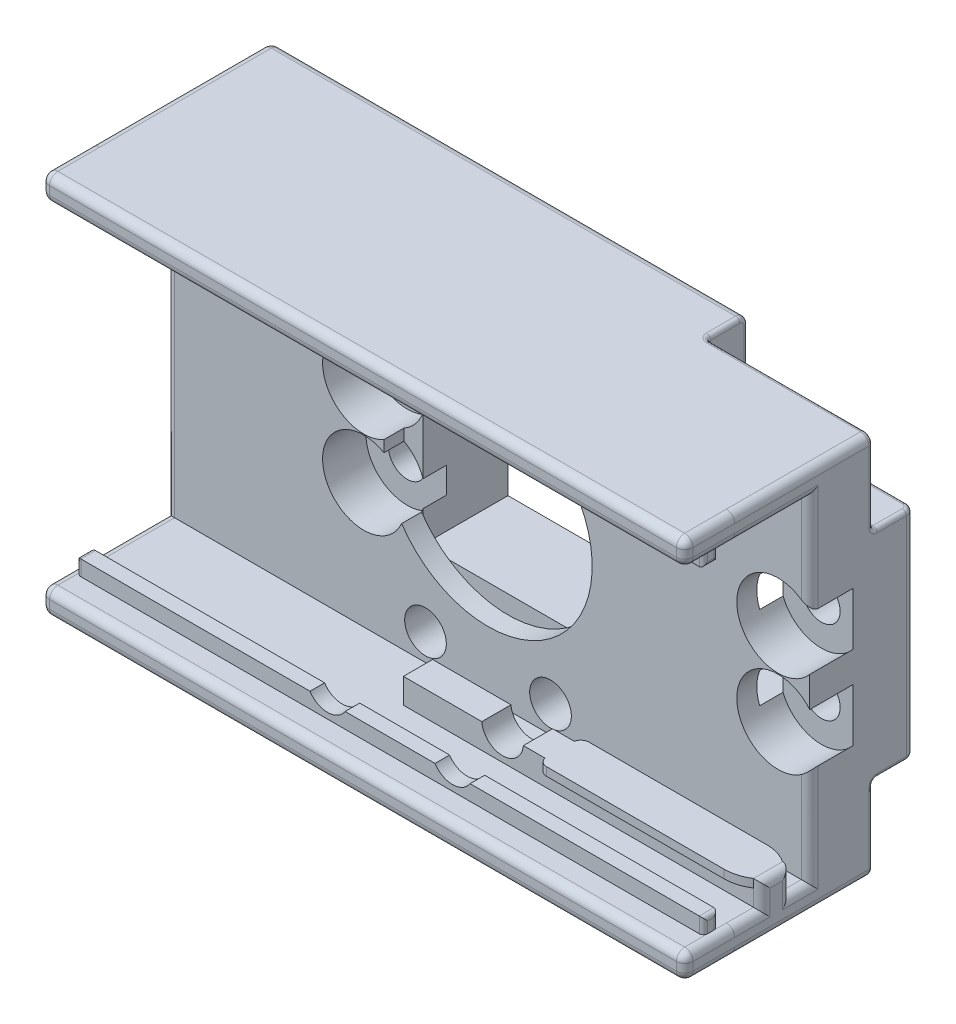
SolidWorks part; units mm, degrees
ref_plane "Front Plane" through (0, 0, 0) normal (0, 0, 1) x (1, 0, 0)
ref_plane "Top Plane" through (0, 0, 0) normal (0, 1, 0) x (1, 0, 0)
ref_plane "Right Plane" through (0, 0, 0) normal (1, 0, 0) x (0, 0, -1)
sketch "Sketch2" plane through (0, 0, 0) normal (0, 0, 1) x (1, 0, 0)
  line L0 (-38.6, 0) -> (38.6, 0) construction
  line L1 (-38.6, 20) -> (38.6, 20)
  line L2 (-38.6, 20) -> (-38.6, -20)
  line L3 (-38.6, -20) -> (38.6, -20)
  line L4 (38.6, 20) -> (38.6, -20)
  line L5 (0, 20) -> (0, -20) construction
  circle A0 centre (0, 0) radius 12.5
  point P13 (0, 0)
  dimension "D1" = 25
  dimension "D2" = 40
  dimension "D3" = 77.2
extrude "Boss-Extrude1" add sketch "Sketch2" along normal blind 2.4
sketch "Sketch5" plane through (0, 0, 0) normal (0, 0, -1) x (-1, 0, 0)
  line L0 (38.6, -20) -> (-38.6, -20) construction
  line L1 (-30.2, 10.3) -> (10.2, 10.3)
  line L2 (-30.2, 10.3) -> (-30.2, -10.3)
  line L3 (-30.2, -10.3) -> (10.2, -10.3)
  line L4 (10.2, 10.3) -> (10.2, -10.3)
  line L5 (-38.6, 20) -> (21.7, 20)
  line L6 (-38.6, 20) -> (-38.6, -20)
  line L7 (-38.6, -20) -> (21.7, -20)
  line L8 (21.7, 20) -> (21.7, -20)
  point P4 (10.2, 0)
  point P13 (-30.2, 0)
  dimension "D1" = 10.2
  dimension "D2" = 30.2
  dimension "D3" = 11.5
  dimension "D4" = 20.6
extrude "Boss-Extrude4" add sketch "Sketch5" along normal blind 10.2
sketch "Sketch6" plane through (0, 0, -10.2) normal (0, 0, -1) x (-1, 0, 0)
  line L1 (-36.1, -0.85) -> (-30.2, -0.85)
  line L2 (-36.1, -0.85) -> (-36.1, 0.85)
  line L3 (-36.1, 0.85) -> (-30.2, 0.85)
  line L4 (-30.2, -0.85) -> (-30.2, 0.85)
  line L5 (-30.2, 10.3) -> (-30.2, -10.3) construction
  dimension "D1" = 1.7
  dimension "D2" = 5.9
extrude "Cut-Extrude1" cut sketch "Sketch6" against normal blind 2
sketch "Sketch9" plane through (0, 20, 0) normal (0, 1, 0) x (1, 0, 0)
  line L0 (-21.7, 10.2) -> (38.6, 10.2) construction
  line L1 (-38.6, 10.2) -> (4.4, 10.2)
  line L2 (-38.6, 10.2) -> (-38.6, -12.4)
  line L3 (-38.6, -12.4) -> (4.4, -12.4)
  line L4 (4.4, 10.2) -> (4.4, -12.4)
  line L5 (38.6, -2.4) -> (-38.6, -2.4) construction
  line L9 (-38.6, -2.4) -> (-38.6, 0) construction
  dimension "D1" = 10
  dimension "D2" = 43
extrude "Boss-Extrude7" add sketch "Sketch9" along normal blind 3
sketch "Sketch10" plane through (0, 20, 0) normal (0, -1, 0) x (1, 0, 0)
  line L0 (4.4, 12.4) -> (4.4, 2.4) construction
  line L1 (-38.6, 8.15) -> (4.4, 8.15)
  line L2 (-38.6, 8.15) -> (-38.6, 4.65)
  line L3 (-38.6, 4.65) -> (4.4, 4.65)
  line L4 (4.4, 8.15) -> (4.4, 4.65)
  line L5 (-38.6, 12.4) -> (4.4, 12.4) construction
  dimension "D1" = 3.5
  dimension "D2" = 4.25
extrude "Boss-Extrude8" add sketch "Sketch10" along normal blind 3
sketch "Sketch20" plane through (4.4, 0, 0) normal (1, 0, 0) x (0, 0, -1)
  line L1 (-12.4, 23) -> (10.2, 23)
  line L2 (-12.4, 23) -> (-12.4, 20)
  line L3 (-12.4, 20) -> (10.2, 20)
  line L4 (10.2, 23) -> (10.2, 20)
extrude "Boss-Extrude9" add sketch "Sketch20" along normal up to surface (34.2 mm away) up to face at (38.6, 0, -3.9)
hole_wizard "Ø4.0mm Dowel Hole1" positions "Sketch12" profile "Sketch13" hole size "Ø4.0" standard "ANSI Metric" end condition through all
sketch "Sketch12" plane through (0, 0, -10.2) normal (0, 0, -1) x (-1, 0, 0)
  line L5 (-38.6, 23) -> (-38.6, -20) construction
  line L7 (10.2, -10.3) -> (10.2, 10.3) construction
  point P0 (-34.8, 5)
  point P10 (-34.8, -5)
  point P12 (14.9, -5)
  point P14 (14.9, 5)
  dimension "D1" = 3.8
  dimension "D2" = 4.7
sketch "Sketch13" plane through (34.8, 5, -10.2) normal (1, 0, 0) x (0, 1, 0)
  line L0 (0, 0) -> (0, 22.6)
  line L1 (0, 22.6) -> (2.25, 22.6)
  line L2 (2.25, 22.6) -> (2.25, 0)
  line L5 (2.25, 0) -> (0, 0)
  line L11 (0, -6.35) -> (0, 107.95) construction
  dimension "Thru Hole Dia." = 4.5
  dimension "Thru Hole Depth" = 22.6
sketch "Sketch17" plane through (0, 0, -10.2) normal (0, 0, -1) x (-1, 0, 0)
  line L0 (-15, 20.3) -> (15, 20.3) construction
  line L1 (15, 20.3) -> (15, 10.3) construction
  line L2 (15, 10.3) -> (-15, 10.3) construction
  line L3 (-15, 10.3) -> (-15, 20.3) construction
  line L4 (10.2, 10.3) -> (-30.2, 10.3) construction
  point P2 (0, 10.3)
  dimension "D1" = 10
  dimension "D2" = 30
hole_wizard "Ø2.0mm Dowel Hole1" positions "Sketch18" profile "Sketch19" hole size "Ø2.0" standard "ANSI Metric" end condition through all
sketch "Sketch18" plane through (0, 0, -10.2) normal (0, 0, -1) x (-1, 0, 0)
  line L3 (-7.5, 16.8) -> (7.5, 16.8) construction
  line L6 (-38.6, 23) -> (38.6, 23) construction
  point P0 (-7.5, 16.8)
  point P2 (7.5, 16.8)
  point P16 (0, 16.8)
  dimension "D1" = 15
  dimension "D2" = 6.2
sketch "Sketch19" plane through (7.5, 16.8, -10.2) normal (1, 0, 0) x (0, 1, 0)
  line L0 (0, 0) -> (0, 22.6)
  line L1 (0, 22.6) -> (1, 22.6)
  line L2 (1, 22.6) -> (1, 0)
  line L5 (1, 0) -> (0, 0)
  line L11 (0, -6.35) -> (0, 107.95) construction
  dimension "Thru Hole Dia." = 2
  dimension "Thru Hole Depth" = 22.6
mirror "Mirror10" about plane through (0, 0, 0) normal (0, 1, 0) of "Ø2.0mm Dowel Hole1"
pattern_circular "CirPattern1" count 2 over 360 about axis through (0, 0, 0) along (0, 0, 1) of "Boss-Extrude7", "Boss-Extrude8"
sketch "Sketch14" plane through (0, 0, 2.4) normal (0, 0, 1) x (1, 0, 0)
  circle A0 centre (-14.9, 5) radius 4.95
  circle A1 centre (-14.9, -5) radius 4.95
  circle A2 centre (-7.5, 16.8) radius 2.5
  circle A3 centre (7.5, 16.8) radius 2.5
  circle A9 centre (34.8, 5) radius 4.95
  circle A11 centre (34.8, -5) radius 4.95
  circle A12 centre (-7.5, -16.8) radius 2.5
  circle A13 centre (7.5, -16.8) radius 2.5
  dimension "D1" = 9.9
  dimension "D2" = 5
extrude "Cut-Extrude2" cut sketch "Sketch14" against normal blind 5.2 and the other way through all
sketch "Sketch22" plane through (-4.4, 0, 0) normal (-1, 0, 0) x (0, 0, 1)
  line L0 (12.4, -23) -> (12.4, -20) construction
  line L1 (-10.2, -23) -> (12.4, -23)
  line L2 (-10.2, -23) -> (-10.2, -20)
  line L3 (-10.2, -20) -> (12.4, -20)
  line L4 (12.4, -23) -> (12.4, -20)
  line L5 (12.4, -20) -> (8.15, -20) construction
extrude "Boss-Extrude10" add sketch "Sketch22" along normal up to surface (34.2 mm away) up to face at (-38.6, 13.3333, 2.9)
fillet "Fillet1" radius 1 39 edges at (38.6, 23, 1.1) (38.6, 20, 7.4) (38.6, -14.0861, 2.4) (38.6, -20, 3.525) (0, -20, 12.4) (38.6, -23, 1.1) (0, -23, 12.4) (0, -23, -10.2) (38.6, -20, 10.275) (38.6, -18.5, 8.15) (38.6, -18.5, 4.65) (38.6, -17, 6.4) (-30.15, 20, 0) (38.6, 14.0861, 2.4) (38.6, 0, -10.2) (-21.7, 0, -10.2) (-21.7, 0, 0) (-21.7, -20, -5.1) (-38.6, -20, -5.1) (-38.6, -20, 7.4) (-38.6, -21.5, 12.4) (-38.6, -23, 1.1) (-30.15, -20, -10.2) (-21.7, 20, -5.1) (-38.6, 0, 2.4) (-30.15, -20, 0) (-38.6, 0, 0) (-38.6, 20, -5.1) (-38.6, 20, 3.525) (0, 20, 12.4) (-38.6, 21.5, 12.4) (-30.15, 20, -10.2) (-38.6, 23, 1.1) (0, 23, 12.4) (0, 23, -10.2) (-38.6, 20, 10.275) (-38.6, 18.5, 8.15) (-38.6, 18.5, 4.65) (-38.6, 17, 6.4)
sketch "Sketch23" plane through (0, 0, -10.2) normal (0, 0, -1) x (-1, 0, 0)
  line L0 (-37.6, 23) -> (37.6, 23) construction
  line L1 (-18.6, 13) -> (-38.6, 13)
  line L2 (-18.6, 13) -> (-18.6, 23)
  line L3 (-18.6, 23) -> (-38.6, 23)
  line L4 (-38.6, 13) -> (-38.6, 23)
  line L5 (-18.6, -13) -> (-38.6, -13)
  line L6 (-18.6, -13) -> (-18.6, -23)
  line L7 (-18.6, -23) -> (-38.6, -23)
  line L8 (-38.6, -13) -> (-38.6, -23)
  line L9 (-38.6, -22) -> (-38.6, 22) construction
  line L10 (37.6, -23) -> (-37.6, -23) construction
  dimension "D1" = 20
  dimension "D2" = 10
  dimension "D3" = 20
  dimension "D4" = 10
extrude "Cut-Extrude3" cut sketch "Sketch23" against normal blind 5
fillet "Fillet2" radius 0.5 24 edges at (18.6, 22.7071, -9.9071) (38.3071, 22.7071, -5.2) (38.3071, -13, -9.9071) (38.3071, 13, -9.9071) (38.3071, -22.7071, -5.2) (18.6, -22.7071, -9.9071) (28.1, 23, -5.2) (28.1, 13, -10.2) (18.6, 17.5, -10.2) (18.6, 18, -5.2) (18.6, 23, -7.2) (28.6, 13, -5.2) (18.6, 13, -7.7) (38.6, 17.5, -5.2) (38.6, 13, -7.2) (18.6, -18, -5.2) (18.6, -13, -7.7) (28.1, -23, -5.2) (18.6, -23, -7.2) (38.6, -17.5, -5.2) (28.6, -13, -5.2) (38.6, -13, -7.2) (18.6, -17.5, -10.2) (28.1, -13, -10.2)
sketch "Sketch24" plane through (0, 0, 4.65) normal (0, 0, -1) x (-1, 0, 0)
  line L1 (37.6, 17) -> (12.6, 17)
  line L2 (37.6, 17) -> (37.6, 18)
  line L3 (37.6, 18) -> (12.6, 18)
  line L4 (12.6, 17) -> (12.6, 18)
  dimension "D1" = 1
  dimension "D2" = 25
extrude "Boss-Extrude11" add sketch "Sketch24" along normal blind 0.8
sketch "Sketch25" plane through (0, 0, 8.15) normal (0, 0, 1) x (1, 0, 0)
  line L1 (-37.6, 17) -> (-12.6, 17)
  line L2 (-37.6, 17) -> (-37.6, 18)
  line L3 (-37.6, 18) -> (-12.6, 18)
  line L4 (-12.6, 17) -> (-12.6, 18)
  dimension "D1" = 25
  dimension "D2" = 1
extrude "Boss-Extrude12" add sketch "Sketch25" along normal blind 0.8
fillet "Fillet3" radius 5 2 edges at (-37.6, 17.5, 3.85) (-37.6, 17.5, 8.95)
sketch "Sketch26" plane through (0, 0, 8.15) normal (0, 0, 1) x (1, 0, 0)
  line L1 (37.6, -17) -> (12.6, -17)
  line L2 (37.6, -17) -> (37.6, -18)
  line L3 (37.6, -18) -> (12.6, -18)
  line L4 (12.6, -17) -> (12.6, -18)
  dimension "D1" = 1
  dimension "D2" = 25
extrude "Boss-Extrude13" add sketch "Sketch26" along normal blind 0.8
sketch "Sketch27" plane through (0, 0, 4.65) normal (0, 0, -1) x (-1, 0, 0)
  line L1 (-37.6, -17) -> (-12.6, -17)
  line L2 (-37.6, -17) -> (-37.6, -18)
  line L3 (-37.6, -18) -> (-12.6, -18)
  line L4 (-12.6, -17) -> (-12.6, -18)
  dimension "D1" = 25
  dimension "D2" = 1
extrude "Boss-Extrude14" add sketch "Sketch27" along normal blind 0.8
fillet "Fillet4" radius 5 2 edges at (37.6, -17.5, 3.85) (37.6, -17.5, 8.95)
fillet "Fillet5" radius 1 4 edges at (12.6, -17.5, 3.85) (12.6, -17.5, 8.95) (-12.6, 17.5, 3.85) (-12.6, 17.5, 8.95)
sketch "Sketch28" plane through (0, 0, 12.4) normal (0, 0, 1) x (1, 0, 0)
  line L0 (-38.6, -21) -> (-38.6, 21) construction
  line L1 (-38.6, -20) -> (38.6, -20)
  line L2 (-38.6, -20) -> (-38.6, -23)
  line L3 (-38.6, -23) -> (38.6, -23)
  line L4 (38.6, -20) -> (38.6, -23)
  line L5 (37.6, -23) -> (-37.6, -23) construction
  line L6 (-37.6, -20) -> (37.6, -20) construction
  line L7 (38.6, -22) -> (38.6, -21) construction
  line L8 (-38.6, 18) -> (-38.6, 21) construction
  line L9 (-38.6, 20) -> (38.6, 20)
  line L10 (-38.6, 20) -> (-38.6, 23)
  line L11 (-38.6, 23) -> (38.6, 23)
  line L12 (38.6, 20) -> (38.6, 23)
  line L13 (-37.6, 23) -> (37.6, 23) construction
  line L14 (4.4, 20) -> (-37.6, 20) construction
  line L15 (38.6, 22) -> (38.6, 21) construction
extrude "Boss-Extrude15" add sketch "Sketch28" along normal blind 5 and the other way blind 1
fillet "Fillet6" radius 1 32 edges at (-38.6, -23, 14.4) (-38.6, -20.5, 11.4) (-38.6, -22.5, 11.4) (-38.6, -20, 14.4) (38.1, -20, 11.4) (-38.1, -20, 11.4) (38.6, -20.5, 11.4) (38.6, -20, 14.4) (38.6, -22.5, 11.4) (38.6, -23, 14.4) (-38.1, -23, 11.4) (38.1, -23, 11.4) (-38.6, -21.5, 17.4) (0, -23, 17.4) (38.6, -21.5, 17.4) (0, -20, 17.4) (-38.6, 20, 14.4) (-38.6, 22.5, 11.4) (-38.6, 20.5, 11.4) (-38.6, 23, 14.4) (38.1, 23, 11.4) (-38.1, 23, 11.4) (38.6, 23, 14.4) (38.6, 20.5, 11.4) (38.6, 22.5, 11.4) (38.6, 20, 14.4) (-38.1, 20, 11.4) (38.1, 20, 11.4) (-38.6, 21.5, 17.4) (0, 20, 17.4) (38.6, 21.5, 17.4) (0, 23, 17.4)
sketch "Sketch29" plane through (0, -20, 0) normal (0, 1, 0) x (1, 0, 0)
  line L0 (-37.6, -11.4) -> (-37.6, -16.4) construction
  line L1 (-37.6, -14.15) -> (37.6, -14.15)
  line L2 (-37.6, -14.15) -> (-37.6, -12.4)
  line L3 (-37.6, -12.4) -> (37.6, -12.4)
  line L4 (37.6, -14.15) -> (37.6, -12.4)
  line L5 (-37.6, -16.4) -> (37.6, -16.4) construction
  line L6 (37.6, -16.4) -> (37.6, -11.4) construction
  dimension "D2" = 1.75
  dimension "D3" = 2.25
extrude "Boss-Extrude16" add sketch "Sketch29" along normal blind 1.85
fillet "Fillet7" radius 0.5 6 edges at (37.6, -19.075, 12.4) (37.6, -18.15, 13.275) (37.6, -19.075, 14.15) (-37.6, -19.075, 12.4) (-37.6, -19.075, 14.15) (-37.6, -18.15, 13.275)
sketch "Sketch30" plane through (0, 20, 0) normal (0, -1, 0) x (1, 0, 0)
  line L0 (37.6, 11.4) -> (37.6, 16.4) construction
  line L1 (37.6, 12.4) -> (-37.6, 12.4)
  line L2 (37.6, 12.4) -> (37.6, 14.15)
  line L3 (37.6, 14.15) -> (-37.6, 14.15)
  line L4 (-37.6, 12.4) -> (-37.6, 14.15)
  line L5 (37.6, 16.4) -> (-37.6, 16.4) construction
  line L6 (-37.6, 16.4) -> (-37.6, 11.4) construction
  dimension "D2" = 1.75
  dimension "D3" = 2.25
extrude "Boss-Extrude17" add sketch "Sketch30" along normal blind 1.85
fillet "Fillet8" radius 0.5 6 edges at (37.6, 19.075, 12.4) (37.6, 18.15, 13.275) (37.6, 19.075, 14.15) (-37.6, 19.075, 12.4) (-37.6, 18.15, 13.275) (-37.6, 19.075, 14.15)
sketch "Sketch31" plane through (0, 0, 14.15) normal (0, 0, 1) x (1, 0, 0)
  circle A0 centre (7.5, -16.8) radius 2.5 construction
  circle A1 centre (-7.5, -16.8) radius 2.5 construction
  circle A2 centre (7.5, 16.8) radius 2.5 construction
  circle A3 centre (-7.5, 16.8) radius 2.5 construction
  circle A4 centre (7.5, -16.8) radius 2.5
  circle A5 centre (-7.5, -16.8) radius 2.5
  circle A6 centre (7.5, 16.8) radius 2.5
  circle A7 centre (-7.5, 16.8) radius 2.5
extrude "Cut-Extrude4" cut sketch "Sketch31" against normal up to surface (1.75 mm away) up to face at (0, 19.075, 12.4)
